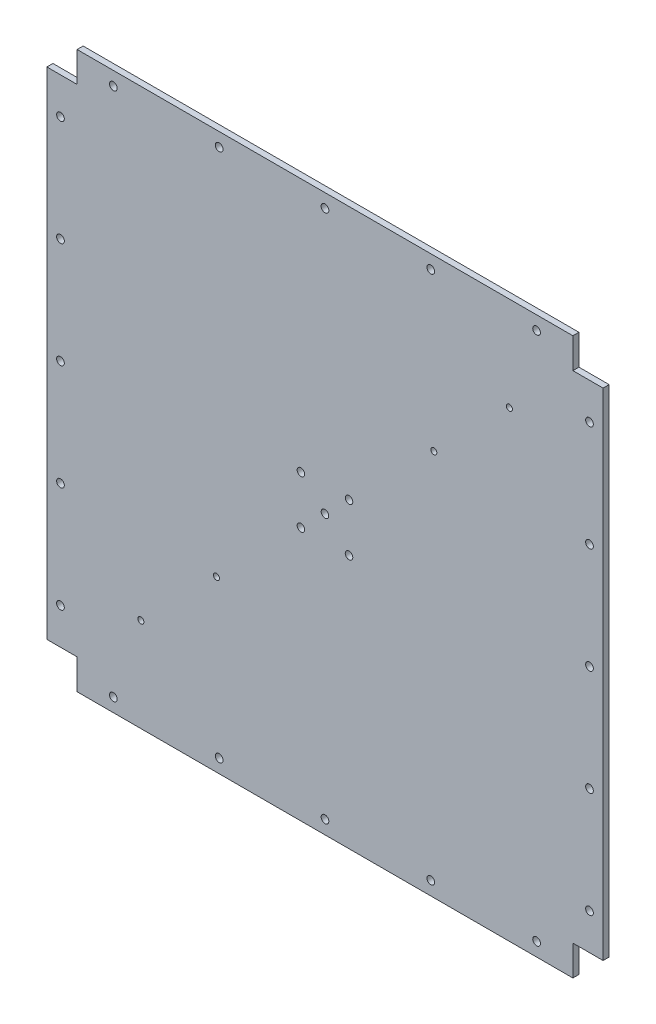
SolidWorks part; units mm, degrees
ref_plane "前视基准面" through (0, 0, 0) normal (0, 0, 1) x (1, 0, 0)
ref_plane "上视基准面" through (0, 0, 0) normal (0, 1, 0) x (1, 0, 0)
ref_plane "右视基准面" through (0, 0, 0) normal (1, 0, 0) x (0, 0, -1)
sketch "草图1" plane through (0, 0, 0) normal (0, 0, 1) x (1, 0, 0)
  line L1 (184, -184) -> (-184, -184)
  line L2 (184, -184) -> (184, 184)
  line L3 (184, 184) -> (-184, 184)
  line L4 (-184, -184) -> (-184, 184)
  line L5 (184, -184) -> (-184, 184) construction
  line L6 (184, 184) -> (-184, -184) construction
  point P0 (0, 0)
  dimension "D1" = 368
  dimension "D2" = 368
extrude "凸台-拉伸1" add sketch "草图1" along normal blind 4
sketch "草图3" plane through (0, 0, 4) normal (0, 0, 1) x (1, 0, 0)
  line L0 (0, -184) -> (0, -175) construction
  line L1 (-184, -184) -> (184, -184) construction
  line L2 (184, 184) -> (-184, 184) construction
  line L3 (-184, 184) -> (-184, -184) construction
  circle A0 centre (0, -175) radius 2.55
  circle A1 centre (70, -175) radius 2.55
  circle A2 centre (140, -175) radius 2.55
  circle A3 centre (-70, -175) radius 2.55
  circle A4 centre (-140, -175) radius 2.55
  circle A30 centre (-175, 140) radius 2.55
  circle A31 centre (-175, 70) radius 2.55
  circle A32 centre (-175, -70) radius 2.55
  circle A33 centre (-175, -140) radius 2.55
  circle A34 centre (-175, 0) radius 2.55
  circle A35 centre (140, 175) radius 2.55
  circle A36 centre (70, 175) radius 2.55
  circle A37 centre (-70, 175) radius 2.55
  circle A38 centre (-140, 175) radius 2.55
  circle A39 centre (0, 175) radius 2.55
  circle A40 centre (175, -140) radius 2.55
  circle A41 centre (175, -70) radius 2.55
  circle A42 centre (175, 70) radius 2.55
  circle A43 centre (175, 140) radius 2.55
  circle A44 centre (175, 0) radius 2.55
  point P38 (0, 0)
  point P39 (0, 0)
  point P47 (10, -10)
  point P78 (0, 0)
  dimension "D1" = 5.1
  dimension "D2" = 9
  dimension "D5" = 9
  dimension "D7" = 44
  dimension "D8" = 9
  dimension "D3" = 3
  dimension "D4" = 3
  dimension "D6" = 4
extrude "切除-拉伸2" cut sketch "草图3" against normal through all
sketch "草图4" plane through (0, 0, 4) normal (0, 0, 1) x (1, 0, 0)
  line L0 (-164, 184) -> (-164, 164)
  line L1 (-184, -184) -> (-164, -184)
  line L2 (-184, -184) -> (-184, -164)
  line L3 (-184, -164) -> (-164, -164)
  line L4 (-164, -184) -> (-164, -164)
  line L5 (-184, 164) -> (-164, 164)
  line L6 (-184, 184) -> (-164, 184)
  line L7 (-184, 184) -> (-184, 164)
  line L8 (184, 164) -> (164, 164)
  line L9 (164, 184) -> (164, 164)
  line L10 (184, 184) -> (184, 164)
  line L11 (184, 184) -> (164, 184)
  line L12 (164, -184) -> (164, -164)
  line L13 (184, -164) -> (164, -164)
  line L14 (184, -184) -> (164, -184)
  line L15 (184, -184) -> (184, -164)
  point P20 (0, 0)
  dimension "D1" = 20
  dimension "D2" = 20
  dimension "D3" = 4
extrude "切除-拉伸3" cut sketch "草图4" against normal through all contours L0 L5 L7 L6 | L8 L9 L11 L10 | L12 L13 L15 L14 | L2 L1 L4 L3
sketch "草图5" plane through (0, 0, 4) normal (0, 0, 1) x (1, 0, 0)
  line L0 (-184, 0) -> (184, 0) construction
  line L1 (-184, 164) -> (-184, -164) construction
  line L3 (0, 184) -> (0, -184) construction
  line L4 (164, 184) -> (-164, 184) construction
  line L5 (-164, -184) -> (164, -184) construction
  line L6 (-10, 0) -> (-22.5, 0) construction
  line L11 (10, -10) -> (-10, 10) construction
  line L12 (10, 10) -> (-10, -10) construction
  line L13 (0, -10) -> (0, -22.5) construction
  line L14 (10, 0) -> (22.5, 0) construction
  line L15 (0, 10) -> (0, 22.5) construction
  line L16 (-173.9781, 173.9781) -> (0, 0) construction
  line L17 (-184, 0) -> (0, 184) construction
  line L18 (0, 0) -> (-15.9099, 15.9099) construction
  line L19 (-14.489, 14.489) -> (-159.489, 14.489) construction
  line L20 (-14.489, 14.489) -> (-14.489, 159.489) construction
  line L21 (-14.489, 159.489) -> (-159.489, 159.489) construction
  line L22 (-159.489, 14.489) -> (-159.489, 159.489) construction
  line L23 (-14.489, 14.489) -> (-159.489, 159.489) construction
  line L24 (-14.489, 159.489) -> (-159.489, 14.489) construction
  line L25 (0, 0) -> (15.9099, 15.9099) construction
  circle A4 centre (0, 0) radius 2.5
  circle A5 centre (-15.9099, 15.9099) radius 2.5
  circle A7 centre (15.9099, 15.9099) radius 2.5
  circle A8 centre (15.9099, -15.9099) radius 2.5
  circle A9 centre (-15.9099, -15.9099) radius 2.5
  point P4 (-86.989, 86.989)
  point P12 (0, 0)
  dimension "D11" = 5
  dimension "D16" = 5
  dimension "D17" = 5
  dimension "D1" = 20
  dimension "D2" = 20
  dimension "D3" = 12.5
  dimension "D4" = 12.5
  dimension "D5" = 12.5
  dimension "D6" = 12.5
  dimension "D12" = 145
  dimension "D13" = 145
  dimension "D14" = 22.5
  dimension "D15" = 22.5
extrude "切除-拉伸6" cut sketch "草图5" against normal blind 10
sketch "草图6" plane through (0, 0, 0) normal (0, 0, -1) x (-1, 0, 0)
  line L0 (-164, -164) -> (164, 164)
  circle A0 centre (121.8, -122) radius 2
  circle A1 centre (71.8, -72) radius 2
  circle A2 centre (-122, 121.8) radius 2
  circle A3 centre (-72, 71.8) radius 2
extrude "切除-拉伸7" cut sketch "草图6" against normal blind 10 contours A2 | A3 | A1 | A0
